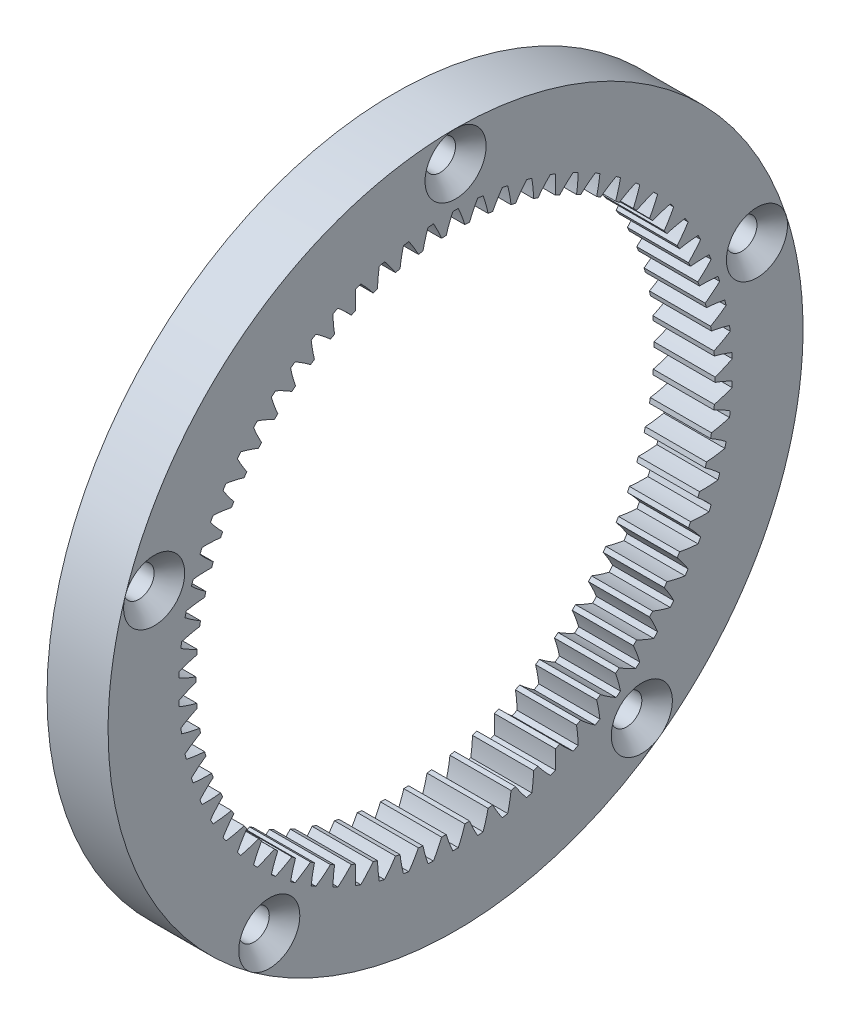
SolidWorks part; units mm, degrees
ref_plane "Plane1" through (0, 0, 0) normal (0, 0, 1) x (1, 0, 0)
ref_plane "Plane2" through (0, 0, 0) normal (0, 1, 0) x (1, 0, 0)
ref_plane "Plane3" through (0, 0, 0) normal (1, 0, 0) x (0, 0, -1)
sketch "HoldingSke" plane through (0, 0, 0) normal (0, 1, 0) x (1, 0, 0)
  line L0 (0, 0) -> (0.684, -1.8794)
  line L1 (-15, 0) -> (100, 0) construction
  line L2 (0, 0) -> (-2.1039, 2.3779)
  line L3 (0, 0) -> (-11.863, 4.5341)
  line L4 (0, 0) -> (2.9537, 8.1152)
  line L5 (0, 0) -> (-23.7986, -8.8762)
  line L6 (0, 0) -> (-10.5278, -7.1032)
  line L7 (-2.1039, 2.3779) -> (3.3635, 27.1825)
  line L8 (-76.2, 2.8779) -> (-54.61, 2.8779)
  line L9 (-71.009, 38.7566) -> (-53.1078, 45.2721)
  line L10 (-76.2, 71.12) -> (104.1128, 71.12)
  line L11 (0, 0) -> (-4, 0)
  line L12 (-76.2, 101.6) -> (-76.181, 101.6)
  line L13 (24.9733, 27.94) -> (52.9518, 28.4284)
  line L14 (24.9733, 27.94) -> (24.9743, 27.94)
  line L15 (24.9733, 27.94) -> (100.4006, 29.5858)
  circle A0 centre (0, 0) radius 22.75
  circle A1 centre (0, 0) radius 12.7
  circle A2 centre (0, 0) radius 12.7
  dimension "MHD" = 25.4
  dimension "Hub_dia" = 25.4
  dimension "Diameter" = 45.5
  dimension "Num_teeth" = 70
  dimension "Pitch_radius" = 180.3128
  dimension "Pitch" = 2
  dimension "Width" = 4
  dimension "Overall_len" = 25.4
  dimension "Show_teeth" = 70
  dimension "Thickness" = 12.7
  dimension "OAL" = 25.4001
  dimension "T_dim" = 21.59
  dimension "Ap" = 20
  dimension "H" = 19.05
  dimension "Backlash" = 0.019
  dimension "Addendum_fac" = 1
  dimension "Dedendum_fac" = 1.25
  dimension "Clearance_fac" = 0.25
  dimension "Dedendum_add" = 0.001
  dimension "Module" = 0.5
sketch "BasProSke" plane through (0, 0, 0) normal (0, 1, 0) x (1, 0, 0)
  line L0 (-10, 0) -> (60, 0) construction
  line L1 (0, 17) -> (0, 22.75)
  line L2 (0, 17) -> (4, 17)
  line L3 (4, 17) -> (4, 22.75)
  line L4 (4, 22.75) -> (0, 22.75)
  dimension "Diameter" = 45.5
  dimension "Thickness" = 4
  dimension "Inside_diameter" = 34
revolve "Base-Revolve" add sketch "BasProSke" angle 360 about L0
sketch "TooCutSke" plane through (0, 0, 0) normal (1, 0, 0) x (0, 0, -1)
  line L3 (0.4402, 17.4945) -> (0.4402, 53.6633) construction
  line L4 (0, 0) -> (0, 59.563) construction
  line L5 (0, 0) -> (-3.0655, 68.2587) construction
  line L6 (-7.7691, 14.4662) -> (37.1407, 16.4831) construction
  circle A0 centre (0, 0) radius 17.5 construction
  circle A1 centre (0, 0) radius 18.126 construction
  circle A2 centre (0, 0) radius 14.8002 construction
  circle A3 centre (0, 0) radius 16.9746 construction
  arc A4 (0.617, 16.9634) -> (0.1792, 18.1251) centre (-7.7691, 14.4662) ccw
  arc A5 (0.617, 16.9634) -> (-0.617, 16.9634) centre (0, 0) ccw
  arc A6 (0.1792, 18.1251) -> (-0.1792, 18.1251) centre (0, 0) ccw
  arc A7 (-0.1792, 18.1251) -> (-0.617, 16.9634) centre (7.7691, 14.4662) ccw
  dimension "Pitch_dia" = 35
  dimension "Base_dia" = 29.6003
  dimension "Root_dia" = 36.252
  dimension "Overcut_dia" = 33.9492
  dimension "Flank_rad" = 8.75
  dimension "Half_ang" = 2.571
  dimension "Half_CT" = 0.4402
extrude "ToothCut" cut sketch "TooCutSke" along normal through all
fillet "Breaks" [suppressed] radius 0.05
fillet "RootFillets" [suppressed] radius 0.126
pattern_circular "TeethCuts" count 70 every 5.143 about axis through (-10, 0, 0) along (1, 0, 0) of "RootFillets", "Breaks", "ToothCut"
sketch "Sketch1" plane through (4, 0, 0) normal (1, 0, 0) x (0, 0, -1)
  circle A0 centre (0, 20.75) radius 1
  circle A1 centre (0, 0) radius 22.75 construction
  dimension "D1" = 20.75
  dimension "D2" = 2
extrude "Cut-Extrude1" cut sketch "Sketch1" against normal up to next
chamfer "Chamfer1" distance 1 angle 45 1 edges at (4, 20.75, -1)
pattern_circular "CirPattern2" count 5 over 360 about axis through (4, 0, 0) along (-1, 0, 0) of "Chamfer1", "Cut-Extrude1"
equation "' \"Module@HoldingSke\" = 6.35"
equation "' \"Num_teeth@HoldingSke\" = 24"
equation "' \"Ap@HoldingSke\" =  14.5"
equation "' \"Width@HoldingSke\" = 12"
equation "' \"Diameter@HoldingSke\" = 8 * 25.4"
equation "' \"Show_teeth@HoldingSke\" = 100"
equation "' \"Backlash@HoldingSke\" = 0.009 * 25.4"
equation "' \"Addendum_fac@HoldingSke\" = 1.0"
equation "' \"Dedendum_fac@HoldingSke\" = 1.25"
equation "' \"Dedendum_add@HoldingSke\" = 0.00005 * 25.4"
equation "' \"Clearance_fac@HoldingSke\" = 0.25"
equation "\"Pitch@HoldingSke\" = 1 / \"Module@HoldingSke\" "
equation "\"Overcut_dia@TooCutSke\" = (\"Num_teeth@HoldingSke\" - 2 * \"Addendum_fac@HoldingSke\") / \"Pitch@HoldingSke\" - 0.002 * 25.4"
equation "\"Pitch_dia@TooCutSke\" = \"Num_teeth@HoldingSke\" / \"Pitch@HoldingSke\""
equation "\"Base_dia@TooCutSke\" = \"Num_teeth@HoldingSke\" / \"Pitch@HoldingSke\" * cos((\"Ap@HoldingSke\"  * 3.14159265 / 180)) * 0.90"
equation "\"Root_dia@TooCutSke\" = \"Num_teeth@HoldingSke\"  / \"Pitch@HoldingSke\" + 2 *  \"Dedendum_fac@HoldingSke\"/ \"Pitch@HoldingSke\" + \"Dedendum_add@HoldingSke\" * 2"
equation "\"Half_ang@TooCutSke\" = 180 / \"Num_teeth@HoldingSke\""
equation "\"Half_CT@TooCutSke\" = \"Num_teeth@HoldingSke\" / \"Pitch@HoldingSke\" * sin((3.14159265 / 2 / \"Num_teeth@HoldingSke\")) / 2 + 10 * \"Backlash@HoldingSke\" / 4"
equation "\"Flank_rad@TooCutSke\" = \"Num_teeth@HoldingSke\" / \"Pitch@HoldingSke\" / 4"
equation "\"Radius@RootFillets\"= \"Clearance_fac@HoldingSke\" / \"Pitch@HoldingSke\" + \"Dedendum_add@HoldingSke\""
equation "\"Break_rad@Breaks\" = 0.02 / \"Pitch@HoldingSke\" * 5"
equation "\"Num_teeth@TeethCuts\" = int( \"Show_teeth@HoldingSke\" ) + 1"
equation "\"Num_teeth@TeethCuts\" = ((sgn( \"Num_teeth@TeethCuts\" - \"Num_teeth@HoldingSke\" )-1)*( \"Num_teeth@TeethCuts\" - \"Num_teeth@HoldingSke\" ))/-2+ \"Num_teeth@HoldingSke\""
equation "\"Num_teeth@TeethCuts\" = ((sgn( \"Num_teeth@TeethCuts\" - 2.0)+1)*( \"Num_teeth@TeethCuts\" - 2.0))/2 +2.0"
equation "\"Angle@TeethCuts\" = 360.0 / \"Num_teeth@HoldingSke\""
equation "\"Diameter@BasProSke\" = \"Num_teeth@HoldingSke\"  / \"Pitch@HoldingSke\" + 2 *  \"Dedendum_fac@HoldingSke\"/ \"Pitch@HoldingSke\" + \"Dedendum_add@HoldingSke\" * 2 + 0.002 * 25.4"
equation "\"Diameter@BasProSke\" = ((sgn( \"Diameter@BasProSke\"  - \"Diameter@HoldingSke\" )+1)*( \"Diameter@BasProSke\"  - \"Diameter@HoldingSke\" ))/2 + \"Diameter@HoldingSke\""
equation "\"Inside_diameter@BasProSke\" =  (\"Num_teeth@HoldingSke\" - 2 * \"Addendum_fac@HoldingSke\") / \"Pitch@HoldingSke\" "
equation "\"Thickness@BasProSke\"  = \"Width@HoldingSke\""
